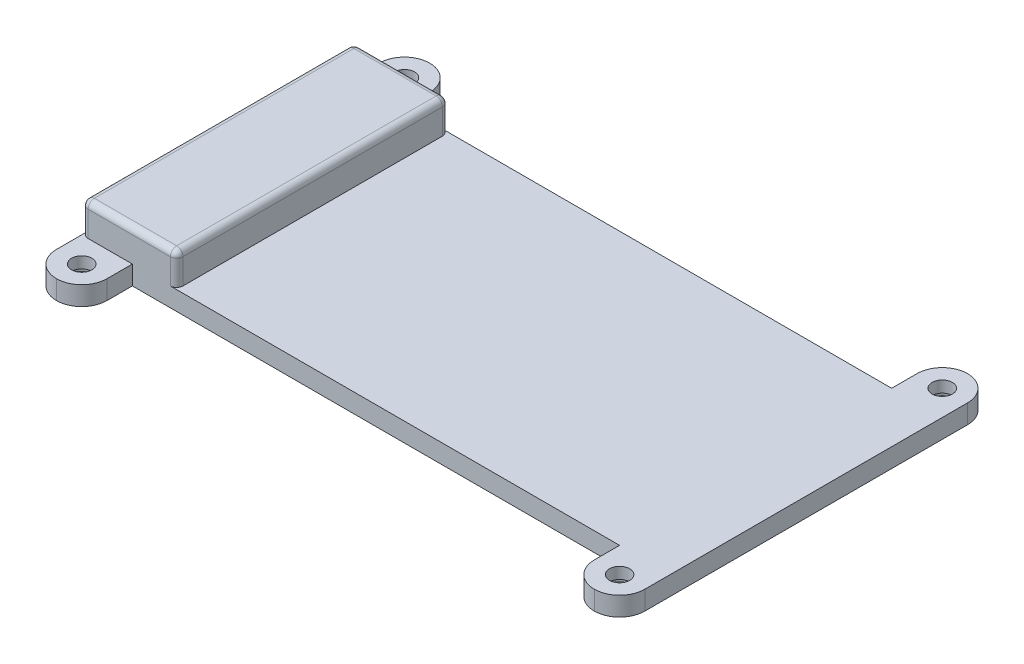
SolidWorks part; units mm, degrees
ref_plane "前视基准面" through (0, 0, 0) normal (0, 0, 1) x (1, 0, 0)
ref_plane "上视基准面" through (0, 0, 0) normal (0, 1, 0) x (1, 0, 0)
ref_plane "右视基准面" through (0, 0, 0) normal (1, 0, 0) x (0, 0, -1)
other "Configuration Table"
sketch "草图1" plane through (0, 0, 0) normal (0, 1, 0) x (1, 0, 0)
  line L0 (-38.5, -21.5) -> (38.5, -21.5)
  line L5 (-46.5, -21.5) -> (-46.5, 21.5)
  line L6 (-38.5, 21.5) -> (38.5, 21.5)
  line L7 (46.5, -21.5) -> (46.5, 21.5)
  line L8 (-46.5, -21.5) -> (46.5, 21.5) construction
  line L9 (-46.5, 21.5) -> (46.5, -21.5) construction
  line L10 (0, 0) -> (0, 21.5) construction
  line L12 (46.5, 21.5) -> (46.5, 29.5)
  line L13 (46.5, 29.5) -> (38.5, 29.5)
  line L14 (38.5, 21.5) -> (38.5, 29.5)
  line L15 (0, 0) -> (46.5, 0) construction
  line L16 (46.5, -29.5) -> (38.5, -29.5)
  line L17 (38.5, -21.5) -> (38.5, -29.5)
  line L19 (46.5, -21.5) -> (46.5, -29.5)
  line L21 (-38.5, -21.5) -> (-38.5, -29.5)
  line L22 (-46.5, -29.5) -> (-38.5, -29.5)
  line L23 (-46.5, -21.5) -> (-46.5, -29.5)
  line L24 (-46.5, 29.5) -> (-38.5, 29.5)
  line L25 (-38.5, 21.5) -> (-38.5, 29.5)
  line L27 (-46.5, 21.5) -> (-46.5, 29.5)
  point P0 (0, 0)
  dimension "D1" = 43
  dimension "D2" = 93
  dimension "D3" = 8
  dimension "D4" = 8
extrude "凸台-拉伸1" add sketch "草图1" along normal blind 3
fillet "圆角1" radius 4 8 edges at (38.5, 1.5, 29.5) (46.5, 1.5, 29.5) (-46.5, 1.5, 29.5) (-38.5, 1.5, 29.5) (-46.5, 1.5, -29.5) (-38.5, 1.5, -29.5) (38.5, 1.5, -29.5) (46.5, 1.5, -29.5)
sketch "草图2" plane through (0, 0, 0) normal (0, -1, 0) x (1, 0, 0)
  line L0 (0, 0) -> (0, 21.5) construction
  line L1 (-38.5, 21.5) -> (38.5, 21.5) construction
  line L2 (0, 0) -> (46.5, 0) construction
  line L3 (46.5, 25.5) -> (46.5, -25.5) construction
  circle A0 centre (42.5, 25.5) radius 1.6
  circle A2 centre (42.5, -25.5) radius 1.6
  circle A3 centre (-42.5, -25.5) radius 1.6
  circle A4 centre (-42.5, 25.5) radius 1.6
  dimension "D1" = 3.2
extrude "切除-拉伸1" cut sketch "草图2" against normal blind 3
sketch "草图3" plane through (0, 0, 0) normal (0, -1, 0) x (1, 0, 0)
  line L0 (0, 0) -> (46.5, 0) construction
  line L1 (0, 21.5) -> (0, 0.3593) construction
  line L2 (-38.5, 21.5) -> (38.5, 21.5) construction
  line L3 (0, 0) -> (0, 21.5) construction
  circle A4 centre (-42.5, 25.5) radius 2.8
  circle A5 centre (42.5, 25.5) radius 2.8
  circle A6 centre (42.5, 25.5) radius 2.8
  circle A7 centre (42.5, -25.5) radius 2.8
  circle A8 centre (-42.5, -25.5) radius 2.8
  dimension "D1" = 1.2
extrude "切除-拉伸2" cut sketch "草图3" against normal blind 1.2
sketch "草图4" plane through (0, 3, 0) normal (0, 1, 0) x (1, 0, 0)
  line L0 (38.5, 21.5) -> (-38.5, 21.5) construction
  line L1 (-31.5, 21.5) -> (-46.5, 21.5)
  line L2 (-31.5, 21.5) -> (-31.5, -21.5)
  line L3 (-31.5, -21.5) -> (-46.5, -21.5)
  line L4 (-46.5, 21.5) -> (-46.5, -21.5)
  line L5 (-46.5, 25.5) -> (-46.5, -25.5) construction
  line L6 (-38.5, -21.5) -> (38.5, -21.5) construction
  dimension "D1" = 15
extrude "凸台-拉伸2" add sketch "草图4" along normal blind 5
fillet "圆角2" radius 1 8 edges at (-39, 8, 21.5) (-46.5, 8, 0) (-39, 8, -21.5) (-31.5, 8, 0) (-31.5, 5.5, 21.5) (-46.5, 5.5, 21.5) (-31.5, 5.5, -21.5) (-46.5, 5.5, -21.5)
